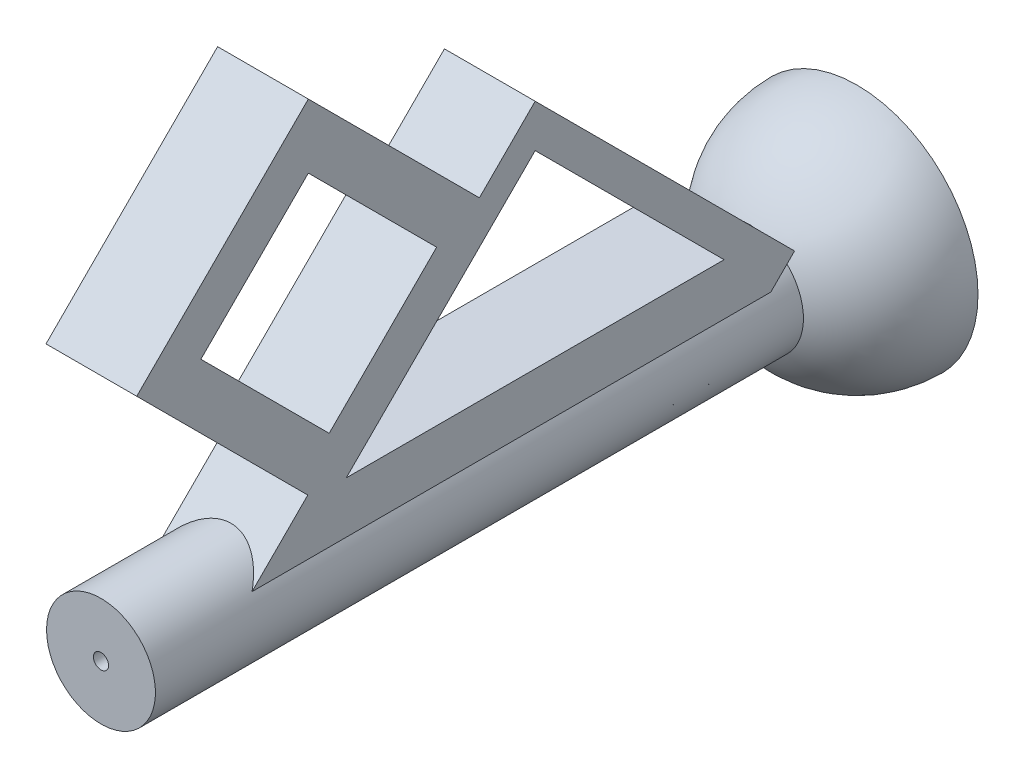
SolidWorks part; units mm, degrees
ref_plane "Front Plane" through (0, 0, 0) normal (0, 0, 1) x (1, 0, 0)
ref_plane "Top Plane" through (0, 0, 0) normal (0, 1, 0) x (1, 0, 0)
ref_plane "Right Plane" through (0, 0, 0) normal (1, 0, 0) x (0, 0, -1)
sketch "Sketch2" plane through (0, 0, 0) normal (0, 0, 1) x (1, 0, 0)
  line L0 (0, -35) -> (0, 35) construction
  line L1 (0, 40) -> (0, 35)
  line L2 (0, -35) -> (0, -40)
  arc A0 (0, 40) -> (0, -40) centre (0, 0) ccw
  arc A1 (0, 35) -> (0, -35) centre (0, 0) ccw
  dimension "D1" = 35
  dimension "D2" = 40
revolve "Revolve2" add sketch "Sketch2" angle 180 about L0
sketch "Sketch3" plane through (0, 0, 0) normal (0, 0, -1) x (-1, 0, 0)
  circle A0 centre (0, 0) radius 17
  dimension "D1" = 34
extrude "Cut-Extrude1" cut sketch "Sketch3" against normal up to surface (36.2077 mm away) up to face at (-40, 0, 0)
ref_plane "Plane1" through (0, 0, 250) normal (0, 0, -1) x (-1, 0, 0)
sketch "Sketch4" plane through (0, 0, 250) normal (0, 0, -1) x (-1, 0, 0)
  circle A0 centre (0, 0) radius 15
  circle A1 centre (0, 0) radius 18
  dimension "D1" = 36
  dimension "D2" = 30
extrude "Boss-Extrude2" add sketch "Sketch4" along normal up to surface (212.919 mm away) up to face at (-17, 0, 36.2077)
sketch "Sketch5" plane through (0, 0, 250) normal (0, 0, 1) x (1, 0, 0)
  circle A0 centre (0, 0) radius 18
extrude "Boss-Extrude3" add sketch "Sketch5" against normal blind 40
sketch "Sketch6" plane through (0, 0, 250) normal (0, 0, 1) x (1, 0, 0)
  circle A0 centre (0, 0) radius 2.5
  dimension "D1" = 5
extrude "Cut-Extrude2" cut sketch "Sketch6" against normal blind 50
sketch "Sketch7" plane through (0, 0, 0) normal (0, 1, 0) x (1, 0, 0)
  line L0 (0, -250) -> (0, 0) construction
  line L1 (-18, -250) -> (18, -250) construction
  line L2 (-124.8157, -125) -> (133.5887, -125) construction
ref_plane "Plane3" through (0, -62.5, 62.5) normal (0, -0.7071, 0.7071) x (1, 0, 0)
ref_plane "Plane4" through (0, -8.9296, 8.9296) normal (0, -0.7071, 0.7071) x (1, 0, 0)
sketch "Sketch9" plane through (0, -8.9296, 8.9296) normal (0, -0.7071, 0.7071) x (1, 0, 0)
  line L0 (15, 37.8039) -> (15, 159.099)
  line L1 (-15, 148.4924) -> (-15, 133.5615) construction
  line L2 (15, 159.099) -> (-15, 159.099)
  line L3 (-15, 159.099) -> (-15, 37.081)
  line L4 (15, 148.4924) -> (15, 141.8586) construction
  line L5 (0, 159.099) -> (-10.0102, 159.099) construction
  arc A0 (40, 0) -> (-40, 0) centre (0, 0) ccw construction
  arc A1 (-15, 37.081) -> (15, 37.8039) centre (0.8932, 0.374) cw
  ellipse E1 centre (0, 148.4924) end of major axis (15, 148.4924) minor radius 10.6066 construction
extrude "Boss-Extrude4" add sketch "Sketch9" along normal up to surface (132.3994 mm away) separate body up to face at (-18, 0, 250)
sketch "Sketch11" plane through (-15, 0, 0) normal (-1, 0, 0) x (0, 0, 1)
  line L0 (58.9512, 26.9499) -> (121.4296, 89.4283)
  line L1 (121.4296, 89.4283) -> (183.908, 26.9499)
  line L2 (183.908, 26.9499) -> (58.9512, 26.9499)
  line L3 (121.4296, 103.5704) -> (35.1498, 17.2906) construction
  line L4 (215.0501, 9.9499) -> (121.4296, 103.5704) construction
  line L5 (250, 18) -> (35.7211, 18) construction
  line L6 (215.0501, 9.9499) -> (42.4906, 9.9499) construction
  dimension "D1" = 10
  dimension "D2" = 10
  dimension "D3" = 17
extrude "Cut-Extrude4" cut sketch "Sketch11" against normal through all
sketch "Sketch12" plane through (0, 112.5, 112.5) normal (0, 0.7071, 0.7071) x (1, 0, 0)
  line L0 (-15, -12.6283) -> (15, -145.0278) construction
  line L1 (15, -12.6283) -> (-15, -145.0278) construction
  line L2 (-15, -145.0278) -> (-15, -12.6283) construction
  line L3 (15, -118.9526) -> (-15, -118.9526)
  line L4 (15, -118.9526) -> (15, -38.7035)
  line L5 (15, -38.7035) -> (-15, -38.7035)
  line L6 (-15, -118.9526) -> (-15, -38.7035)
  line L7 (15, -118.9526) -> (-15, -38.7035) construction
  line L8 (15, -38.7035) -> (-15, -118.9526) construction
  point P8 (0, -78.8281)
  point P9 (0, -78.8281)
extrude "Boss-Extrude5" add sketch "Sketch12" along normal blind 80
sketch "Sketch13" plane through (-15, 0, 0) normal (-1, 0, 0) x (0, 0, 1)
  line L0 (189.5411, 42.5299) -> (154.0096, 78.0614)
  line L1 (154.0096, 78.0614) -> (196.4361, 120.4878)
  line L2 (196.4361, 120.4878) -> (231.9675, 84.9563)
  line L3 (231.9675, 84.9563) -> (189.5411, 42.5299)
  line L4 (253.1807, 84.9563) -> (196.6122, 28.3878) construction
  line L5 (183.908, 26.9499) -> (121.4296, 89.4283) construction
  line L6 (196.4361, 141.701) -> (139.8675, 85.1325) construction
  line L7 (196.4361, 141.701) -> (253.1807, 84.9563) construction
  dimension "D1" = 15
  dimension "D2" = 15
  dimension "D3" = 15
  dimension "D4" = 15
extrude "Cut-Extrude5" cut sketch "Sketch13" against normal blind 80
ref_axis "Axis1" through (0, 0, 210) along (0, 0, 1)
